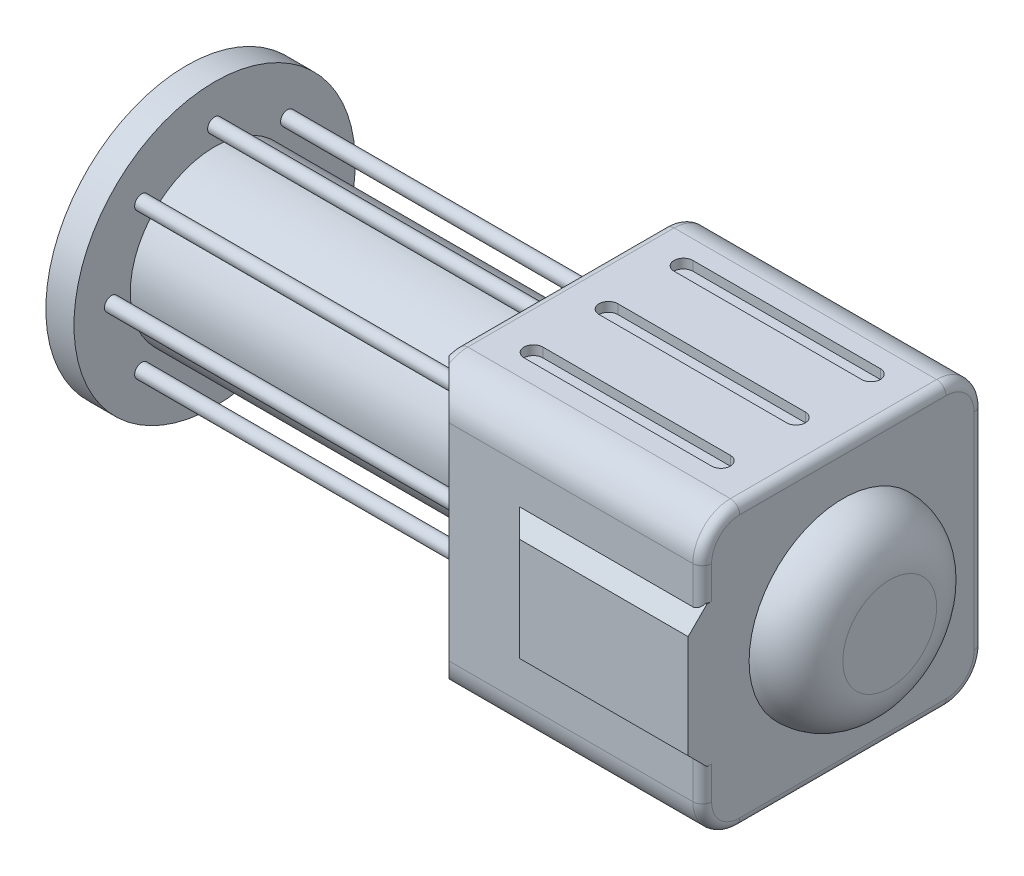
SolidWorks part; units mm, degrees
ref_plane "Front Plane" through (0, 0, 0) normal (0, 0, 1) x (1, 0, 0)
ref_plane "Top Plane" through (0, 0, 0) normal (0, 1, 0) x (1, 0, 0)
ref_plane "Right Plane" through (0, 0, 0) normal (1, 0, 0) x (0, 0, -1)
sketch "Sketch1" plane through (0, 0, 0) normal (0, 1, 0) x (1, 0, 0)
  line L1 (-15, 15) -> (15, 15)
  line L2 (-15, 15) -> (-15, -15)
  line L3 (-15, -15) -> (15, -15)
  line L4 (15, 15) -> (15, -15)
  line L5 (-15, 15) -> (15, -15) construction
  line L6 (-15, -15) -> (15, 15) construction
  point P0 (0, 0)
  dimension "D1" = 30
  dimension "D2" = 30
extrude "Boss-Extrude1" add sketch "Sketch1" along normal mid plane 30
sketch "Sketch2" plane through (0, 0, 0) normal (0, 0, 1) x (1, 0, 0)
  line L0 (-15, 0) -> (-55, 0)
  line L1 (-15, 15) -> (-15, -15) construction
  line L2 (-55, 0) -> (-55, 15)
  line L3 (-55, 15) -> (-52, 15)
  line L4 (-52, 15) -> (-52, 9)
  line L5 (-52, 9) -> (-15, 9)
  line L6 (-15, 9) -> (-15, 0)
  dimension "D1" = 40
  dimension "D2" = 9
  dimension "D3" = 15
  dimension "D4" = 3
revolve "Revolve1" add sketch "Sketch2" angle 360 about L0
fillet "Fillet2" radius 4 4 edges at (0, 15, -15) (0, -15, -15) (0, -15, 15) (0, 15, 15)
chamfer "Chamfer2" distance 3 angle 45 1 edges at (-15, 0, 15)
fillet "Fillet3" radius 1 7 edges at (-15, -14.9681, 11.504) (-15, -15, 0) (-15, -13.8284, -13.8284) (-15, 0, -15) (-15, 13.8284, -13.8284) (-15, 14.9681, 11.504) (-15, 15, 0)
fillet "Fillet4" radius 1 8 edges at (15, 13.8284, 13.8284) (15, 0, 15) (15, -13.8284, 13.8284) (15, -15, 0) (15, -13.8284, -13.8284) (15, 0, -15) (15, 13.8284, -13.8284) (15, 15, 0)
sketch "Sketch3" plane through (15, 0, 0) normal (1, 0, 0) x (0, 0, -1)
  circle A0 centre (0, 0) radius 10
  dimension "D1" = 20
extrude "Boss-Extrude2" add sketch "Sketch3" along normal blind 5
fillet "Fillet5" radius 5 1 edges at (20, 0, -10)
sketch "Sketch4" plane through (15, 0, 0) normal (1, 0, 0) x (0, 0, -1)
  line L0 (-14, 11) -> (-14, -11) construction
  line L2 (-16.5, 7.5) -> (-11.5, 7.5)
  line L3 (-16.5, 7.5) -> (-16.5, -7.5)
  line L4 (-16.5, -7.5) -> (-11.5, -7.5)
  line L5 (-11.5, 7.5) -> (-11.5, -7.5)
  line L6 (-16.5, 7.5) -> (-11.5, -7.5) construction
  line L7 (-16.5, -7.5) -> (-11.5, 7.5) construction
  point P3 (-14, 0)
  dimension "D1" = 15
  dimension "D2" = 5
extrude "Boss-Extrude3" add sketch "Sketch4" against normal blind 20
chamfer "Chamfer3" distance 2 angle 45 3 edges at (5, -7.5, 16.5) (5, 7.5, 16.5) (-5, 0, 16.5)
sketch "Sketch5" plane through (-55, 0, 0) normal (-1, 0, 0) x (0, 0, 1)
  circle A0 centre (0, 0) radius 5
extrude "Cut-Extrude1" cut sketch "Sketch5" against normal blind 10
sketch "Sketch6" plane through (-55, 0, 0) normal (-1, 0, 0) x (0, 0, 1)
  line L0 (0, 0) -> (0, 11) construction
  circle A0 centre (0, 11) radius 0.75
  dimension "D1" = 11
extrude "Boss-Extrude4" add sketch "Sketch6" against normal up to surface (40 mm away) up to face at (-15, 9, 0)
pattern_circular "CirPattern1" count 8 over 360 about axis through (0, 0, 0) along (1, 0, 0) of "Boss-Extrude4"
sketch "Sketch7" plane through (0, 0, -15) normal (0, 0, -1) x (-1, 0, 0)
  circle A0 centre (0, 0) radius 5
extrude "Cut-Extrude2" cut sketch "Sketch7" against normal blind 10
sketch "Sketch8" plane through (0, 15, 0) normal (0, 1, 0) x (1, 0, 0)
  line L0 (-10, 0) -> (10, 0) construction
  line L1 (-10, 1) -> (10, 1)
  line L2 (-10, -1) -> (10, -1)
  line L3 (-10, -8) -> (10, -8) construction
  line L4 (-10, -7) -> (10, -7)
  line L5 (-10, -9) -> (10, -9)
  line L6 (-10, 0) -> (10, 0) construction
  line L7 (-10, 1) -> (10, 1)
  line L8 (-10, -1) -> (10, -1)
  line L9 (-10, 8) -> (10, 8) construction
  line L10 (-10, 9) -> (10, 9)
  line L11 (-10, 7) -> (10, 7)
  arc A0 (-10, 1) -> (-10, -1) centre (-10, 0) ccw
  arc A1 (10, -1) -> (10, 1) centre (10, 0) ccw
  arc A2 (-10, -7) -> (-10, -9) centre (-10, -8) ccw
  arc A3 (10, -9) -> (10, -7) centre (10, -8) ccw
  arc A4 (-10, 1) -> (-10, -1) centre (-10, 0) ccw
  arc A5 (10, -1) -> (10, 1) centre (10, 0) ccw
  arc A6 (-10, 9) -> (-10, 7) centre (-10, 8) ccw
  arc A7 (10, 7) -> (10, 9) centre (10, 8) ccw
  point P2 (0, 0)
  point P12 (0, -8)
  point P19 (0, 0)
  point P26 (0, 8)
  dimension "D1" = 20
  dimension "D2" = 2
  dimension "D3" = 2
  dimension "D4" = 2
extrude "Cut-Extrude3" cut sketch "Sketch8" against normal blind 1 contours L1 A1 L2 A0
pattern_linear "LPattern1" count 2 spacing 8 along (0, 0, 1) count 2 spacing 8 along (0, 0, -1) of "Cut-Extrude3"
